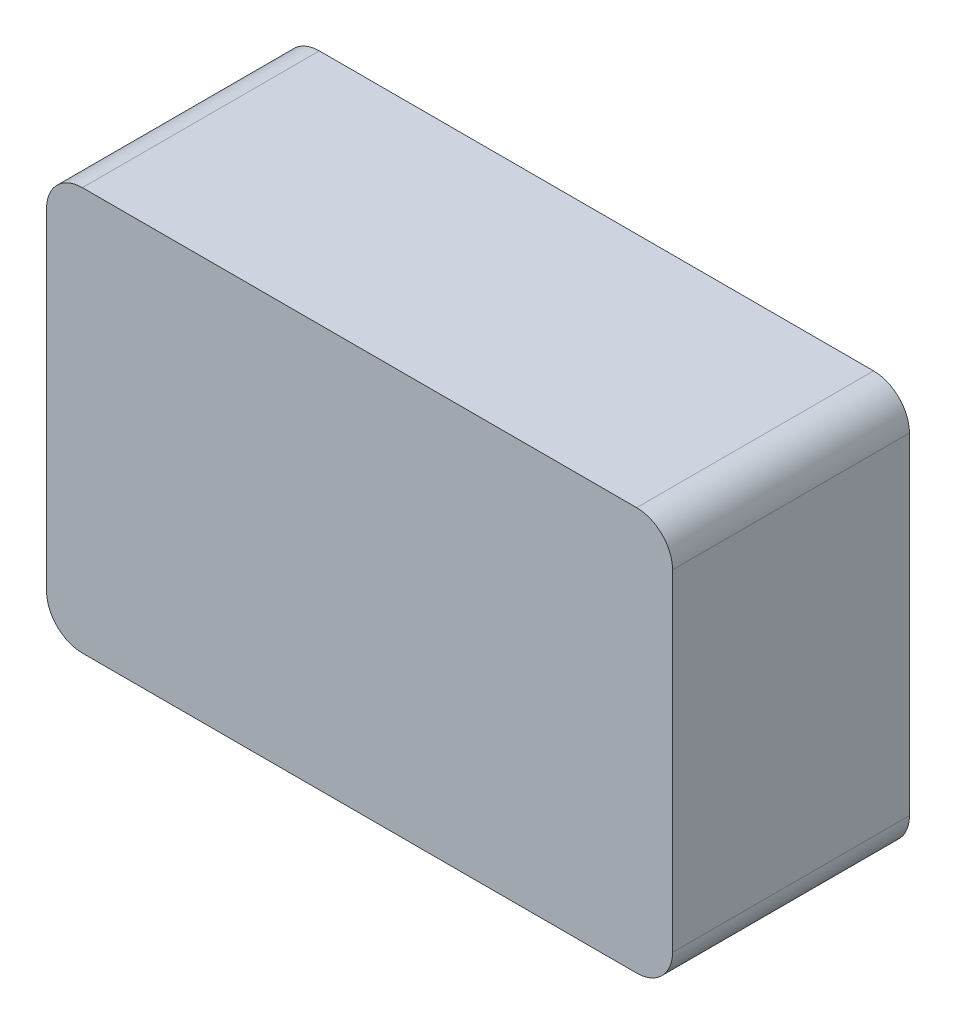
SolidWorks part; units mm, degrees
ref_plane "Front" through (0, 0, 0) normal (0, 0, 1) x (1, 0, 0)
ref_plane "Top" through (0, 0, 0) normal (0, 1, 0) x (1, 0, 0)
ref_plane "Right" through (0, 0, 0) normal (1, 0, 0) x (0, 0, -1)
sketch "Sketch1" plane through (0, 0, 0) normal (0, 0, 1) x (1, 0, 0)
  line L1 (-38.6, -28.075) -> (38.6, -28.075)
  line L2 (-43.6, -23.075) -> (-43.6, 23.075)
  line L3 (-38.6, 28.075) -> (38.6, 28.075)
  line L4 (43.6, -23.075) -> (43.6, 23.075)
  line L5 (-43.6, -28.075) -> (43.6, 28.075) construction
  line L6 (-43.6, 28.075) -> (43.6, -28.075) construction
  arc A0 (-38.6, -28.075) -> (-43.6, -23.075) centre (-38.6, -23.075) cw
  arc A1 (38.6, -28.075) -> (43.6, -23.075) centre (38.6, -23.075) ccw
  arc A2 (38.6, 28.075) -> (43.6, 23.075) centre (38.6, 23.075) cw
  arc A3 (-43.6, 23.075) -> (-38.6, 28.075) centre (-38.6, 23.075) cw
  point P0 (0, 0)
  dimension "D3" = 5
  dimension "D1" = 87.2
  dimension "D2" = 56.15
extrude "Boss-Extrude1" add sketch "Sketch1" along normal blind 33
